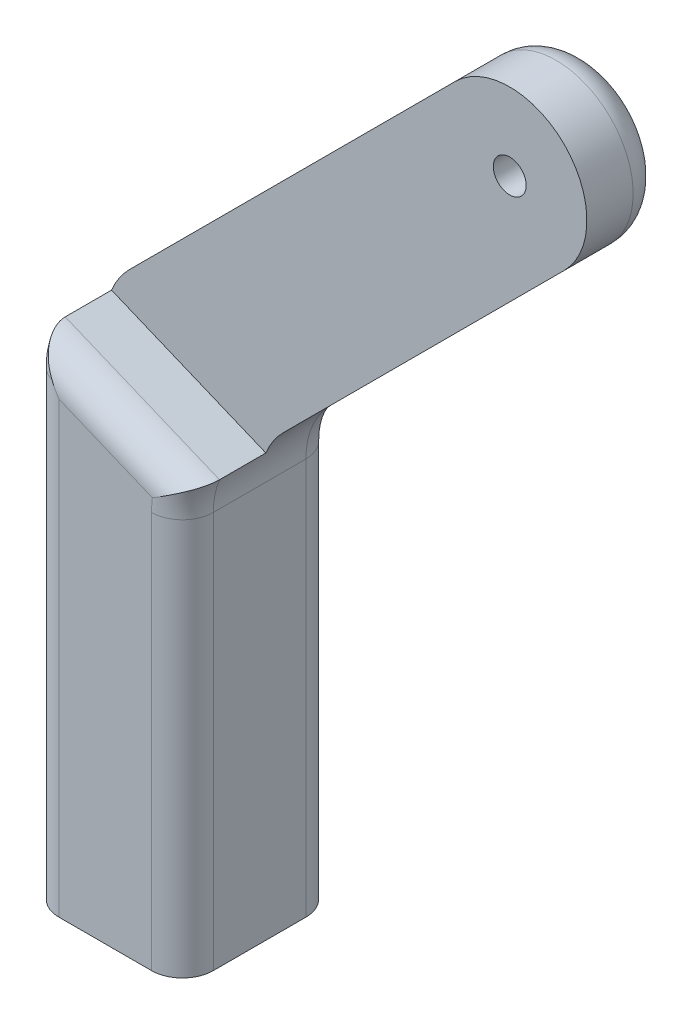
SolidWorks part; units mm, degrees
ref_plane "前视基准面" through (0, 0, 0) normal (0, 0, 1) x (1, 0, 0)
ref_plane "上视基准面" through (0, 0, 0) normal (0, 1, 0) x (1, 0, 0)
ref_plane "右视基准面" through (0, 0, 0) normal (1, 0, 0) x (0, 0, -1)
sketch "Model" plane through (0, 0, 0) normal (0, 0, 1) x (1, 0, 0)
  line L0 (113.5961, 231.9397) -> (128.5961, 231.9397)
  line L1 (128.5961, 231.9397) -> (128.5961, 270.5194)
  line L2 (113.5961, 231.9397) -> (113.5961, 276.7326)
  line L3 (130.9393, 276.1763) -> (158.2193, 303.4562)
  line L4 (115.9393, 282.3895) -> (147.6127, 314.0628)
  arc A0 (115.9393, 282.3895) -> (113.5961, 276.7326) centre (121.5961, 276.7326) ccw
  arc A1 (130.9393, 276.1763) -> (128.5961, 270.5194) centre (136.5961, 270.5194) ccw
  arc A2 (158.2193, 303.4562) -> (147.6127, 314.0628) centre (152.916, 308.7595) ccw
extrude "凸台-拉伸1" add sketch "Model" along normal blind 15
sketch "草图2" plane through (0, 231.9397, 0) normal (0, -1, 0) x (1, 0, 0)
  line L0 (113.5961, 15) -> (128.5961, 15) construction
  line L2 (113.5961, 15) -> (113.5961, 0) construction
  circle A0 centre (121.0961, 7.5) radius 3.1
  point P6 (113.5961, 6.3404)
  dimension "D1" = 6.2
  dimension "D2" = 7.5
  dimension "D3" = 7.5
extrude "切除-拉伸1" cut sketch "草图2" against normal blind 12
sketch "草图3" plane through (0, 0, 15) normal (0, 0, 1) x (1, 0, 0)
  line L0 (114.2051, 279.7941) -> (129.2051, 273.5809)
  line L1 (147.6127, 314.0628) -> (115.9393, 282.3895) construction
  line L2 (130.9393, 276.1763) -> (158.2193, 303.4562) construction
  line L3 (147.6127, 314.0628) -> (115.9393, 282.3895)
  line L4 (130.9393, 276.1763) -> (158.2193, 303.4562)
  arc A0 (115.9393, 282.3895) -> (113.5961, 276.7326) centre (121.5961, 276.7326) ccw construction
  arc A1 (130.9393, 276.1763) -> (128.5961, 270.5194) centre (136.5961, 270.5194) ccw construction
  arc A2 (158.2193, 303.4562) -> (147.6127, 314.0628) centre (152.916, 308.7595) ccw construction
  arc A3 (130.9393, 276.1763) -> (129.2051, 273.5809) centre (136.5961, 270.5194) ccw
  arc A4 (115.9393, 282.3895) -> (114.2051, 279.7941) centre (121.5961, 276.7326) ccw
  arc A5 (158.2193, 303.4562) -> (147.6127, 314.0628) centre (152.916, 308.7595) ccw
extrude "切除-拉伸2" cut sketch "草图3" against normal blind 7.5
sketch "草图4" plane through (0, 0, 7.5) normal (0, 0, 1) x (1, 0, 0)
  circle A0 centre (152.916, 308.7595) radius 1.6
  dimension "D1" = 3.2
extrude "切除-拉伸3" cut sketch "草图4" against normal blind 8
sketch "草图5" plane through (0, 0, 0) normal (0, 0, -1) x (-1, 0, 0)
  line L1 (-149.6828, 308.7595) -> (-151.2994, 311.5595)
  line L2 (-151.2994, 311.5595) -> (-154.5325, 311.5595)
  line L3 (-154.5325, 311.5595) -> (-156.1491, 308.7595)
  line L4 (-156.1491, 308.7595) -> (-154.5325, 305.9595)
  line L5 (-154.5325, 305.9595) -> (-151.2994, 305.9595)
  line L6 (-151.2994, 305.9595) -> (-149.6828, 308.7595)
  circle A0 centre (-152.916, 308.7595) radius 2.8 construction
  dimension "D1" = 5.6
extrude "切除-拉伸4" cut sketch "草图5" against normal blind 3
fillet "圆角1" radius 3 11 edges at (113.5961, 254.3362, 0) (114.2051, 279.7941, 0) (131.776, 298.2261, 0) (158.2193, 314.0628, 0) (144.5793, 289.8162, 0) (129.2051, 273.5809, 0) (128.7499, 272.0801, 15) (128.5961, 251.2296, 0) (128.5961, 251.2296, 15) (121.7051, 276.6875, 15) (113.5961, 254.3362, 15)
